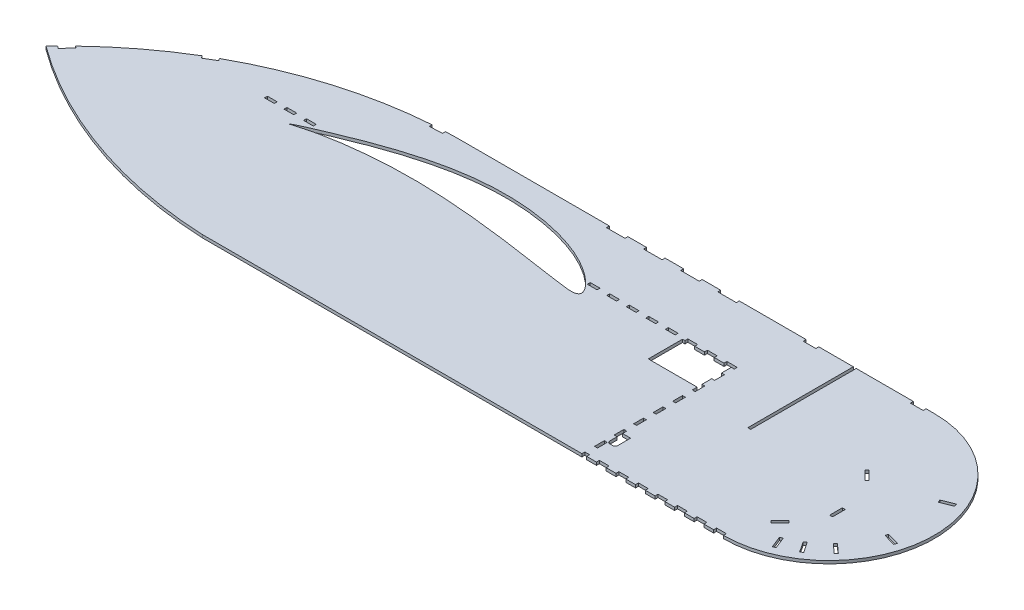
SolidWorks part; units mm, degrees
ref_plane "Front Plane" through (0, 0, 0) normal (0, 0, 1) x (1, 0, 0)
ref_plane "Top Plane" through (0, 0, 0) normal (0, 1, 0) x (1, 0, 0)
ref_plane "Right Plane" through (0, 0, 0) normal (1, 0, 0) x (0, 0, -1)
sketch "Sketch1" plane through (0, 0, 0) normal (0, 1, 0) x (1, 0, 0)
  line L0 (800, 108) -> (0, 108) construction
  line L1 (266.4083, 0) -> (800, 0)
  line L2 (0, 0) -> (0, 216) construction
  line L3 (316.2946, 216) -> (800, 216)
  arc A0 (800, 216) -> (800, 0) centre (800, 108) cw
  arc A2 (266.4083, 0) -> (19.4291, 86.8932) centre (286.1808, 450.645) cw
  arc A4 (19.4291, 86.8932) -> (316.2946, 216) centre (316.2946, -189.8565) cw
  dimension "D1" = 800
  dimension "D2" = 216
extrude "Boss-Extrude1" add sketch "Sketch1" along normal blind 3
sketch "Sketch2" plane through (0, 0, 0) normal (0, -1, 0) x (1, 0, 0)
  line L0 (605.07, -153) -> (605.07, 81) construction
  line L1 (647.57, -153) -> (637.57, -153)
  line L2 (655.07, -153) -> (655.07, -143)
  line L3 (655.07, -118) -> (605.07, -118)
  line L4 (823.6893, -121.2328) -> (814.4969, -130.4252)
  line L5 (814.4969, -130.4252) -> (816.6182, -132.5465)
  line L6 (816.6182, -132.5465) -> (825.8106, -123.3541)
  line L7 (825.8106, -123.3541) -> (823.6893, -121.2328)
  line L8 (823.6893, -121.2328) -> (814.4969, -130.4252)
  line L9 (814.4969, -130.4252) -> (816.6182, -132.5465)
  line L10 (816.6182, -132.5465) -> (825.8106, -123.3541)
  line L11 (825.8106, -123.3541) -> (823.6893, -121.2328)
  line L12 (605.07, -153) -> (605.07, -118)
  line L13 (778.5, -216) -> (791.5, -216) construction
  line L14 (791.5, -216) -> (791.5, -213) construction
  line L15 (791.5, -213) -> (778.5, -213) construction
  line L16 (778.5, -213) -> (778.5, -216) construction
  line L17 (668.6076, -216) -> (681.6076, -216) construction
  line L18 (681.6076, -216) -> (681.6076, -213) construction
  line L19 (681.6076, -213) -> (668.6076, -213) construction
  line L20 (833.1606, -28.1059) -> (837.9352, -16.0144)
  line L21 (837.9352, -16.0144) -> (835.1449, -14.9126)
  line L22 (835.1449, -14.9126) -> (830.3703, -27.0041)
  line L23 (830.3703, -27.0041) -> (833.1606, -28.1059)
  line L24 (833.1606, -28.1059) -> (837.9352, -16.0144)
  line L25 (837.9352, -16.0144) -> (835.1449, -14.9126)
  line L26 (835.1449, -14.9126) -> (830.3703, -27.0041)
  line L27 (830.3703, -27.0041) -> (833.1606, -28.1059)
  line L28 (839.4566, -85.3169) -> (839.4566, -72.3169)
  line L29 (839.4566, -72.3169) -> (836.4566, -72.3169)
  line L30 (836.4566, -72.3169) -> (836.4566, -85.3169)
  line L31 (836.4566, -85.3169) -> (839.4566, -85.3169)
  line L32 (839.4566, -85.3169) -> (839.4566, -72.3169)
  line L33 (839.4566, -72.3169) -> (836.4566, -72.3169)
  line L34 (836.4566, -72.3169) -> (836.4566, -85.3169)
  line L35 (836.4566, -85.3169) -> (839.4566, -85.3169)
  line L36 (668.6076, -213) -> (668.6076, -216) construction
  line L39 (600.2018, -213) -> (581.2018, -213) construction
  line L40 (658.07, -25.4734) -> (658.07, -38.6734)
  line L41 (663.77, -22.9734) -> (660.57, -22.9734)
  line L42 (666.27, -38.6734) -> (666.27, -25.4734)
  line L43 (658.07, -38.6734) -> (666.27, -38.6734)
  line L44 (658.07, -25.4734) -> (658.07, -33)
  line L45 (663.77, -22.9734) -> (660.57, -22.9734)
  line L46 (666.27, -38.6734) -> (666.27, -25.4734)
  line L47 (658.07, -38.6734) -> (666.27, -38.6734)
  line L48 (581.2018, -213) -> (581.2018, -216) construction
  line L49 (581.2018, -216) -> (600.2018, -216) construction
  line L50 (600.2018, -216) -> (600.2018, -213) construction
  line L51 (562.2018, -213) -> (543.2018, -213) construction
  line L52 (543.2018, -213) -> (543.2018, -216) construction
  line L53 (543.2018, -216) -> (562.2018, -216) construction
  line L54 (562.2018, -216) -> (562.2018, -213) construction
  line L55 (524.2018, -213) -> (505.2018, -213) construction
  line L56 (505.2018, -213) -> (505.2018, -216) construction
  line L57 (505.2018, -216) -> (524.2018, -216) construction
  line L58 (524.2018, -216) -> (524.2018, -213) construction
  line L59 (486.2018, -213) -> (467.2018, -213) construction
  line L60 (467.2018, -213) -> (467.2018, -216) construction
  line L61 (467.2018, -216) -> (486.2018, -216) construction
  line L62 (486.2018, -216) -> (486.2018, -213) construction
  line L63 (286.6536, -215.0679) -> (299.64, -215.6627) construction
  line L64 (299.64, -215.6627) -> (299.7772, -212.6658) construction
  line L65 (299.7772, -212.6658) -> (286.7909, -212.0711) construction
  line L66 (286.7909, -212.0711) -> (286.6536, -215.0679) construction
  line L67 (107.8918, -158.4076) -> (119.0512, -165.0761) construction
  line L68 (119.0512, -165.0761) -> (120.5901, -162.5008) construction
  line L69 (120.5901, -162.5008) -> (109.4307, -155.8323) construction
  line L70 (109.4307, -155.8323) -> (107.8918, -158.4076) construction
  line L71 (25.2251, -93.1105) -> (34.0897, -102.6194) construction
  line L72 (34.0897, -102.6194) -> (36.2841, -100.5738) construction
  line L73 (36.2841, -100.5738) -> (27.4195, -91.0649) construction
  line L74 (27.4195, -91.0649) -> (25.2251, -93.1105) construction
  line L79 (212.57, -142.2618) -> (212.57, -142.2948)
  line L131 (537.57, -153) -> (527.57, -153) construction
  line L132 (527.57, -153) -> (527.57, -156) construction
  line L133 (527.57, -156) -> (537.57, -156) construction
  line L134 (537.57, -156) -> (537.57, -153) construction
  line L135 (557.57, -153) -> (547.57, -153) construction
  line L136 (547.57, -153) -> (547.57, -156) construction
  line L137 (547.57, -156) -> (557.57, -156) construction
  line L138 (557.57, -156) -> (557.57, -153) construction
  line L139 (577.57, -153) -> (567.57, -153) construction
  line L140 (567.57, -153) -> (567.57, -156) construction
  line L141 (567.57, -156) -> (577.57, -156) construction
  line L142 (577.57, -156) -> (577.57, -153) construction
  line L143 (597.57, -153) -> (587.57, -153) construction
  line L144 (587.57, -153) -> (587.57, -156) construction
  line L145 (587.57, -156) -> (597.57, -156) construction
  line L146 (597.57, -156) -> (597.57, -153) construction
  line L148 (607.57, -153) -> (607.57, -156) construction
  line L149 (607.57, -156) -> (617.57, -156) construction
  line L150 (617.57, -156) -> (617.57, -153) construction
  line L152 (627.57, -153) -> (627.57, -156) construction
  line L153 (627.57, -156) -> (637.57, -156) construction
  line L154 (637.57, -156) -> (637.57, -153) construction
  line L155 (658.07, -153) -> (647.57, -153) construction
  line L156 (647.57, -153) -> (647.57, -156) construction
  line L157 (647.57, -156) -> (658.07, -156) construction
  line L158 (658.07, -156) -> (658.07, -153) construction
  line L160 (655.07, -143) -> (658.07, -143) construction
  line L161 (658.07, -143) -> (658.07, -133) construction
  line L162 (658.07, -133) -> (655.07, -133) construction
  line L163 (655.07, -113) -> (655.07, -123) construction
  line L164 (655.07, -123) -> (658.07, -123) construction
  line L165 (658.07, -123) -> (658.07, -113) construction
  line L166 (658.07, -113) -> (655.07, -113) construction
  line L167 (655.07, -93) -> (655.07, -103) construction
  line L168 (655.07, -103) -> (658.07, -103) construction
  line L169 (658.07, -103) -> (658.07, -93) construction
  line L170 (658.07, -93) -> (655.07, -93) construction
  line L171 (655.07, -73) -> (655.07, -83) construction
  line L172 (655.07, -83) -> (658.07, -83) construction
  line L173 (658.07, -83) -> (658.07, -73) construction
  line L174 (658.07, -73) -> (655.07, -73) construction
  line L175 (655.07, -53) -> (655.07, -63) construction
  line L176 (655.07, -63) -> (658.07, -63) construction
  line L177 (658.07, -63) -> (658.07, -53) construction
  line L178 (658.07, -53) -> (655.07, -53) construction
  line L179 (655.07, -33) -> (655.07, -43) construction
  line L180 (655.07, -43) -> (658.07, -43) construction
  line L182 (658.07, -33) -> (655.07, -33) construction
  line L183 (655.07, -13) -> (655.07, -23) construction
  line L184 (655.07, -23) -> (658.07, -23) construction
  line L185 (658.07, -23) -> (658.07, -13) construction
  line L186 (658.07, -13) -> (655.07, -13) construction
  line L187 (660, 0) -> (655.07, 0) construction
  line L188 (879.4887, -142.1211) -> (891.5217, -147.041) construction
  line L189 (891.5217, -147.041) -> (892.6571, -144.2642) construction
  line L190 (892.6571, -144.2642) -> (880.6241, -139.3442) construction
  line L191 (880.6241, -139.3442) -> (879.4887, -142.1211) construction
  line L192 (883.5475, -85.5833) -> (896.0431, -81.9972) construction
  line L193 (896.0431, -81.9972) -> (895.2156, -79.1136) construction
  line L194 (895.2156, -79.1136) -> (882.72, -82.6997) construction
  line L195 (882.72, -82.6997) -> (883.5475, -85.5833) construction
  line L196 (865.3607, -51.3372) -> (875.0343, -42.6526) construction
  line L197 (875.0343, -42.6526) -> (873.0302, -40.4202) construction
  line L198 (873.0302, -40.4202) -> (863.3566, -49.1048) construction
  line L199 (863.3566, -49.1048) -> (865.3607, -51.3372) construction
  line L200 (849.0648, -36.7585) -> (856.2517, -25.9258) construction
  line L201 (856.2517, -25.9258) -> (853.7518, -24.2673) construction
  line L202 (853.7518, -24.2673) -> (846.5649, -35.1) construction
  line L203 (846.5649, -35.1) -> (849.0648, -36.7585) construction
  line L204 (822.4089, -44.7346) -> (813.2165, -35.5422) construction
  line L205 (813.2165, -35.5422) -> (811.0952, -37.6635) construction
  line L206 (811.0952, -37.6635) -> (820.2876, -46.8559) construction
  line L207 (820.2876, -46.8559) -> (822.4089, -44.7346) construction
  line L208 (879.4887, -142.1211) -> (891.5217, -147.041)
  line L209 (891.5217, -147.041) -> (892.6571, -144.2642)
  line L210 (892.6571, -144.2642) -> (880.6241, -139.3442)
  line L211 (880.6241, -139.3442) -> (879.4887, -142.1211)
  line L212 (883.5475, -85.5833) -> (896.0431, -81.9972)
  line L213 (896.0431, -81.9972) -> (895.2156, -79.1136)
  line L214 (895.2156, -79.1136) -> (882.72, -82.6997)
  line L215 (882.72, -82.6997) -> (883.5475, -85.5833)
  line L216 (865.3607, -51.3372) -> (875.0343, -42.6526)
  line L217 (875.0343, -42.6526) -> (873.0302, -40.4202)
  line L218 (873.0302, -40.4202) -> (863.3566, -49.1048)
  line L219 (863.3566, -49.1048) -> (865.3607, -51.3372)
  line L220 (849.0648, -36.7585) -> (856.2517, -25.9258)
  line L221 (856.2517, -25.9258) -> (853.7518, -24.2673)
  line L222 (853.7518, -24.2673) -> (846.5649, -35.1)
  line L223 (846.5649, -35.1) -> (849.0648, -36.7585)
  line L224 (822.4089, -44.7346) -> (813.2165, -35.5422)
  line L225 (813.2165, -35.5422) -> (811.0952, -37.6635)
  line L226 (811.0952, -37.6635) -> (820.2876, -46.8559)
  line L227 (820.2876, -46.8559) -> (822.4089, -44.7346)
  line L228 (655.07, 0) -> (655.07, -3) construction
  line L229 (655.07, -3) -> (660, -3) construction
  line L230 (660, -3) -> (660, 0) construction
  line L231 (680, 0) -> (670, 0) construction
  line L232 (670, 0) -> (670, -3) construction
  line L233 (670, -3) -> (680, -3) construction
  line L234 (680, -3) -> (680, 0) construction
  line L235 (700, 0) -> (690, 0) construction
  line L236 (690, 0) -> (690, -3) construction
  line L237 (690, -3) -> (700, -3) construction
  line L238 (700, -3) -> (700, 0) construction
  line L239 (720, 0) -> (710, 0) construction
  line L240 (710, 0) -> (710, -3) construction
  line L241 (710, -3) -> (720, -3) construction
  line L242 (720, -3) -> (720, 0) construction
  line L243 (740, 0) -> (730, 0) construction
  line L244 (730, 0) -> (730, -3) construction
  line L245 (730, -3) -> (740, -3) construction
  line L246 (740, -3) -> (740, 0) construction
  line L247 (760, 0) -> (750, 0) construction
  line L248 (750, 0) -> (750, -3) construction
  line L249 (750, -3) -> (760, -3) construction
  line L250 (760, -3) -> (760, 0) construction
  line L251 (780, 0) -> (770, 0) construction
  line L252 (770, 0) -> (770, -3) construction
  line L253 (770, -3) -> (780, -3) construction
  line L254 (780, -3) -> (780, 0) construction
  line L255 (800, 0) -> (790, 0) construction
  line L256 (790, 0) -> (790, -3) construction
  line L257 (790, -3) -> (800, -3) construction
  line L258 (800, -3) -> (800, 0) construction
  line L259 (778.5, -216) -> (791.5, -216)
  line L260 (791.5, -216) -> (791.5, -213)
  line L261 (791.5, -213) -> (778.5, -213)
  line L262 (778.5, -213) -> (778.5, -216)
  line L263 (668.6076, -216) -> (681.6076, -216)
  line L264 (681.6076, -216) -> (681.6076, -213)
  line L265 (681.6076, -213) -> (668.6076, -213)
  line L266 (668.6076, -213) -> (668.6076, -216)
  line L267 (600.2018, -213) -> (581.2018, -213)
  line L268 (581.2018, -213) -> (581.2018, -216)
  line L269 (581.2018, -216) -> (600.2018, -216)
  line L270 (600.2018, -216) -> (600.2018, -213)
  line L271 (562.2018, -213) -> (543.2018, -213)
  line L272 (543.2018, -213) -> (543.2018, -216)
  line L273 (543.2018, -216) -> (562.2018, -216)
  line L274 (562.2018, -216) -> (562.2018, -213)
  line L275 (524.2018, -213) -> (505.2018, -213)
  line L276 (505.2018, -213) -> (505.2018, -216)
  line L277 (505.2018, -216) -> (524.2018, -216)
  line L278 (524.2018, -216) -> (524.2018, -213)
  line L279 (486.2018, -213) -> (467.2018, -213)
  line L280 (467.2018, -213) -> (467.2018, -216)
  line L281 (467.2018, -216) -> (486.2018, -216)
  line L282 (486.2018, -216) -> (486.2018, -213)
  line L283 (286.6536, -215.0679) -> (299.64, -215.6627)
  line L284 (299.64, -215.6627) -> (299.7772, -212.6658)
  line L285 (299.7772, -212.6658) -> (286.7909, -212.0711)
  line L286 (286.7909, -212.0711) -> (286.6536, -215.0679)
  line L287 (107.8918, -158.4076) -> (119.0512, -165.0761)
  line L288 (119.0512, -165.0761) -> (120.5901, -162.5008)
  line L289 (120.5901, -162.5008) -> (109.4307, -155.8323)
  line L290 (109.4307, -155.8323) -> (107.8918, -158.4076)
  line L291 (25.2251, -93.1105) -> (34.0897, -102.6194)
  line L292 (34.0897, -102.6194) -> (36.2841, -100.5738)
  line L293 (36.2841, -100.5738) -> (27.4195, -91.0649)
  line L294 (27.4195, -91.0649) -> (25.2251, -93.1105)
  line L351 (537.57, -153) -> (527.57, -153)
  line L352 (527.57, -153) -> (527.57, -156)
  line L353 (527.57, -156) -> (537.57, -156)
  line L354 (537.57, -156) -> (537.57, -153)
  line L355 (557.57, -153) -> (547.57, -153)
  line L356 (547.57, -153) -> (547.57, -156)
  line L357 (547.57, -156) -> (557.57, -156)
  line L358 (557.57, -156) -> (557.57, -153)
  line L359 (577.57, -153) -> (567.57, -153)
  line L360 (567.57, -153) -> (567.57, -156)
  line L361 (567.57, -156) -> (577.57, -156)
  line L362 (577.57, -156) -> (577.57, -153)
  line L363 (597.57, -153) -> (587.57, -153)
  line L364 (587.57, -153) -> (587.57, -156)
  line L365 (587.57, -156) -> (597.57, -156)
  line L366 (597.57, -156) -> (597.57, -153)
  line L368 (607.57, -153) -> (607.57, -156)
  line L369 (607.57, -156) -> (617.57, -156)
  line L370 (617.57, -156) -> (617.57, -153)
  line L372 (627.57, -153) -> (627.57, -156)
  line L373 (627.57, -156) -> (637.57, -156)
  line L374 (637.57, -156) -> (637.57, -153)
  line L375 (658.07, -153) -> (655.07, -153)
  line L376 (647.57, -153) -> (647.57, -156)
  line L377 (647.57, -156) -> (658.07, -156)
  line L378 (658.07, -156) -> (658.07, -153)
  line L380 (655.07, -143) -> (658.07, -143)
  line L381 (658.07, -143) -> (658.07, -133)
  line L382 (658.07, -133) -> (655.07, -133)
  line L383 (655.07, -113) -> (655.07, -118)
  line L384 (655.07, -123) -> (658.07, -123)
  line L385 (658.07, -123) -> (658.07, -113)
  line L386 (658.07, -113) -> (655.07, -113)
  line L387 (655.07, -93) -> (655.07, -103)
  line L388 (655.07, -103) -> (658.07, -103)
  line L389 (658.07, -103) -> (658.07, -93)
  line L390 (658.07, -93) -> (655.07, -93)
  line L391 (655.07, -73) -> (655.07, -83)
  line L392 (655.07, -83) -> (658.07, -83)
  line L393 (658.07, -83) -> (658.07, -73)
  line L394 (658.07, -73) -> (655.07, -73)
  line L395 (655.07, -53) -> (655.07, -63)
  line L396 (655.07, -63) -> (658.07, -63)
  line L397 (658.07, -63) -> (658.07, -53)
  line L398 (658.07, -53) -> (655.07, -53)
  line L399 (655.07, -33) -> (655.07, -43)
  line L400 (655.07, -43) -> (658.07, -43)
  line L401 (658.07, -43) -> (658.07, -38.6734)
  line L402 (658.07, -33) -> (655.07, -33)
  line L403 (655.07, -13) -> (655.07, -23)
  line L404 (655.07, -23) -> (658.07, -23)
  line L405 (658.07, -23) -> (658.07, -13)
  line L406 (658.07, -13) -> (655.07, -13)
  line L407 (660, 0) -> (655.07, 0)
  line L408 (655.07, 0) -> (655.07, -3)
  line L409 (655.07, -3) -> (660, -3)
  line L410 (660, -3) -> (660, 0)
  line L411 (680, 0) -> (670, 0)
  line L412 (670, 0) -> (670, -3)
  line L413 (670, -3) -> (680, -3)
  line L414 (680, -3) -> (680, 0)
  line L415 (700, 0) -> (690, 0)
  line L416 (690, 0) -> (690, -3)
  line L417 (690, -3) -> (700, -3)
  line L418 (700, -3) -> (700, 0)
  line L419 (720, 0) -> (710, 0)
  line L420 (710, 0) -> (710, -3)
  line L421 (710, -3) -> (720, -3)
  line L422 (720, -3) -> (720, 0)
  line L423 (740, 0) -> (730, 0)
  line L424 (730, 0) -> (730, -3)
  line L425 (730, -3) -> (740, -3)
  line L426 (740, -3) -> (740, 0)
  line L427 (760, 0) -> (750, 0)
  line L428 (750, 0) -> (750, -3)
  line L429 (750, -3) -> (760, -3)
  line L430 (760, -3) -> (760, 0)
  line L431 (780, 0) -> (770, 0)
  line L432 (770, 0) -> (770, -3)
  line L433 (770, -3) -> (780, -3)
  line L434 (780, -3) -> (780, 0)
  line L435 (800, 0) -> (790, 0)
  line L436 (790, 0) -> (790, -3)
  line L437 (790, -3) -> (800, -3)
  line L438 (800, -3) -> (800, 0)
  line L439 (655.07, -133) -> (655.07, -123)
  line L440 (627.57, -153) -> (617.57, -153)
  line L441 (607.57, -153) -> (605.07, -153)
  line L462 (187.07, -153) -> (177.07, -153) construction
  line L463 (177.07, -153) -> (177.07, -156) construction
  line L464 (177.07, -156) -> (187.07, -156) construction
  line L465 (187.07, -156) -> (187.07, -153) construction
  line L466 (207.07, -153) -> (197.07, -153) construction
  line L467 (197.07, -153) -> (197.07, -156) construction
  line L468 (197.07, -156) -> (207.07, -156) construction
  line L469 (207.07, -156) -> (207.07, -153) construction
  line L470 (227.07, -153) -> (217.07, -153) construction
  line L471 (217.07, -153) -> (217.07, -156) construction
  line L472 (217.07, -156) -> (227.07, -156) construction
  line L473 (227.07, -156) -> (227.07, -153) construction
  line L474 (517.57, -153) -> (507.57, -153) construction
  line L475 (507.57, -153) -> (507.57, -156) construction
  line L476 (507.57, -156) -> (517.57, -156) construction
  line L477 (517.57, -156) -> (517.57, -153) construction
  line L478 (187.07, -153) -> (177.07, -153)
  line L479 (177.07, -153) -> (177.07, -156)
  line L480 (177.07, -156) -> (187.07, -156)
  line L481 (187.07, -156) -> (187.07, -153)
  line L482 (207.07, -153) -> (197.07, -153)
  line L483 (197.07, -153) -> (197.07, -156)
  line L484 (197.07, -156) -> (207.07, -156)
  line L485 (207.07, -156) -> (207.07, -153)
  line L486 (227.07, -153) -> (217.07, -153)
  line L487 (217.07, -153) -> (217.07, -156)
  line L488 (217.07, -156) -> (227.07, -156)
  line L489 (227.07, -156) -> (227.07, -153)
  line L490 (517.57, -153) -> (507.57, -153)
  line L491 (507.57, -153) -> (507.57, -156)
  line L492 (507.57, -156) -> (517.57, -156)
  line L493 (517.57, -156) -> (517.57, -153)
  line L534 (717, -108) -> (717, -216)
  line L535 (717, -216) -> (720, -216)
  line L536 (720, -216) -> (720, -108)
  line L537 (720, -108) -> (717, -108)
  line L538 (717, -108) -> (717, -216)
  line L539 (717, -216) -> (720, -216)
  line L540 (720, -216) -> (720, -108)
  line L541 (720, -108) -> (717, -108)
  arc A2 (660.57, -22.9734) -> (658.07, -25.4734) centre (660.57, -25.4734) ccw
  arc A3 (666.27, -25.4734) -> (663.77, -22.9734) centre (663.77, -25.4734) ccw
  arc A4 (660.57, -22.9734) -> (658.07, -25.4734) centre (660.57, -25.4734) ccw
  arc A5 (666.27, -25.4734) -> (663.77, -22.9734) centre (663.77, -25.4734) ccw
  spline S1 degree 3 poles (-1490.7318, -2610.4866) (189.7857, -84.8289) (191.8397, -130.1262) (215.6642, -144.2206) (218.7234, -145.7779) (222.7838, -147.5804) (227.7591, -149.7808) (233.6732, -152.3729) (243.3346, -156.474) (254.0716, -160.9286) (265.8113, -165.5514) (275.5598, -169.1926) (285.8203, -172.7897) (300.2132, -177.4429) (315.0475, -181.6144) (330.2168, -185.0782) (341.7168, -187.2628) (353.2384, -188.9705) (364.7498, -190.1898) (376.2222, -190.8893) (387.6115, -191.0869) (398.8538, -190.7647) (413.4214, -189.6963) (427.5808, -187.7) (441.1954, -184.8275) (450.8219, -182.3197) (459.9489, -179.4697) (468.5117, -176.2876) (476.4536, -172.8247) (483.7151, -169.1289) (490.2481, -165.2848) (496.0197, -161.4069) (500.998, -157.5857) (505.1476, -153.8841) (508.4473, -150.3827) (510.8522, -147.1808) (512.2305, -144.519) (512.6724, -142.438) (512.366, -140.694) (510.8363, -139.2679) (508.3008, -138.6046) (504.9907, -138.3969) (500.8451, -138.6329) (495.8864, -139.207) (490.1274, -140.0338) (483.6007, -141.0142) (476.346, -142.082) (468.4189, -143.2709) (459.8696, -144.553) (447.4042, -146.414) (434.3028, -148.292) (413.2306, -151.0803) (394.9165, -153.1705) (372.4131, -155.1852) (353.2786, -156.4974) (334.1039, -157.1205) (318.8375, -157.1193) (307.5693, -156.8631) (296.5448, -156.3424) (285.8536, -155.5986) (275.5863, -154.6546) (265.8296, -153.5569) (256.6735, -152.3128) (248.205, -150.9585) (240.5101, -149.5233) (233.6661, -148.0641) (227.7356, -146.6296) (222.7715, -145.2056) (218.7746, -143.9126) (215.7248, -142.9952) (190.4211, -136.5967) (159.0994, -163.5562) (767.7445, 2804.8334) knots -0.121434 -0.121434 -0.121434 -0.121434 0.001413 0.005226 0.010781 0.017816 0.026461 0.036791 0.048686 0.076639 0.092363 0.109003 0.126387 0.144339 0.181313 0.200023 0.218713 0.237261 0.255692 0.274037 0.292193 0.310133 0.327788 0.362002 0.378421 0.394287 0.409543 0.424114 0.437938 0.450942 0.463044 0.474154 0.484165 0.493024 0.500713 0.507126 0.51213 0.514904 0.517171 0.520262 0.524245 0.529498 0.536092 0.544061 0.553363 0.563905 0.575615 0.58842 0.602227 0.616944 0.648676 0.665501 0.718564 0.736789 0.773513 0.810245 0.828489 0.846493 0.864125 0.881249 0.897725 0.913415 0.928184 0.941897 0.954411 0.965603 0.97535 0.983576 0.990285 0.995433 0.9988 1.114983 1.114983 1.114983 1.114983 only from (212.57, -142.2948) to (212.57, -142.2618) construction
  spline S2 degree 3 poles (212.57, -142.2948) (212.8151, -142.4601) (213.7215, -143.0713) (215.6642, -144.2206) (218.7234, -145.7779) (222.7838, -147.5804) (227.7591, -149.7808) (233.6732, -152.3729) (243.3346, -156.474) (254.0716, -160.9286) (265.8113, -165.5514) (275.5598, -169.1926) (285.8203, -172.7897) (300.2132, -177.4429) (315.0475, -181.6144) (330.2168, -185.0782) (341.7168, -187.2628) (353.2384, -188.9705) (364.7498, -190.1898) (376.2222, -190.8893) (387.6115, -191.0869) (398.8538, -190.7647) (413.4214, -189.6963) (427.5808, -187.7) (441.1954, -184.8275) (450.8219, -182.3197) (459.9489, -179.4697) (468.5117, -176.2876) (476.4536, -172.8247) (483.7151, -169.1289) (490.2481, -165.2848) (496.0197, -161.4069) (500.998, -157.5857) (505.1476, -153.8841) (508.4473, -150.3827) (510.8522, -147.1808) (512.2305, -144.519) (512.6724, -142.438) (512.366, -140.694) (510.8363, -139.2679) (508.3008, -138.6046) (504.9907, -138.3969) (500.8451, -138.6329) (495.8864, -139.207) (490.1274, -140.0338) (483.6007, -141.0142) (476.346, -142.082) (468.4189, -143.2709) (459.8696, -144.553) (447.4042, -146.414) (434.3028, -148.292) (413.2306, -151.0803) (394.9165, -153.1705) (372.4131, -155.1852) (353.2786, -156.4974) (334.1039, -157.1205) (318.8375, -157.1193) (307.5693, -156.8631) (296.5448, -156.3424) (285.8536, -155.5986) (275.5863, -154.6546) (265.8296, -153.5569) (256.6735, -152.3128) (248.205, -150.9585) (240.5101, -149.5233) (233.6661, -148.0641) (227.7356, -146.6296) (222.7715, -145.2056) (218.7746, -143.9126) (215.7248, -142.9952) (213.7534, -142.4967) (212.8162, -142.3107) (212.57, -142.2618) knots 0 0 0 0 0.001413 0.005226 0.010781 0.017816 0.026461 0.036791 0.048686 0.076639 0.092363 0.109003 0.126387 0.144339 0.181313 0.200023 0.218713 0.237261 0.255692 0.274037 0.292193 0.310133 0.327788 0.362002 0.378421 0.394287 0.409543 0.424114 0.437938 0.450942 0.463044 0.474154 0.484165 0.493024 0.500713 0.507126 0.51213 0.514904 0.517171 0.520262 0.524245 0.529498 0.536092 0.544061 0.553363 0.563905 0.575615 0.58842 0.602227 0.616944 0.648676 0.665501 0.718564 0.736789 0.773513 0.810245 0.828489 0.846493 0.864125 0.881249 0.897725 0.913415 0.928184 0.941897 0.954411 0.965603 0.97535 0.983576 0.990285 0.995433 0.9988 1 1 1 1
  dimension "D6" = 35
  dimension "D1" = 0
  dimension "D2" = 0
  dimension "D3" = 0
  dimension "D4" = 0
  dimension "D5" = 0
extrude "Cut-Extrude1" cut sketch "Sketch2" against normal through all
